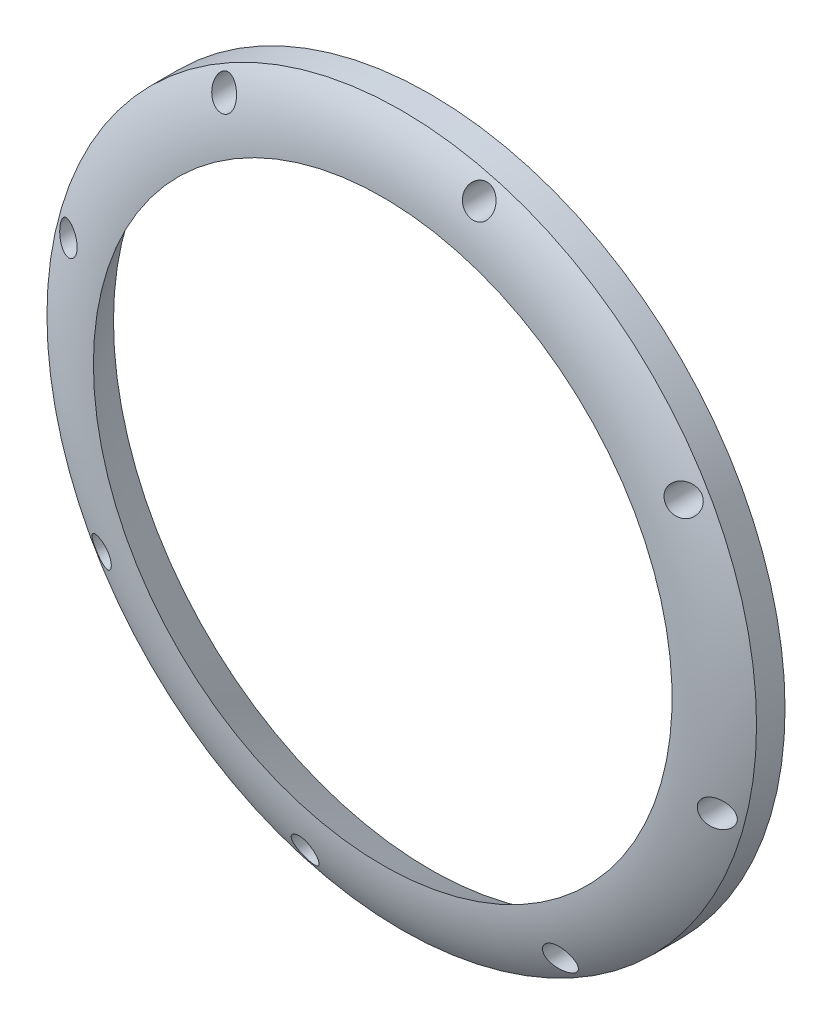
SolidWorks part; units mm, degrees
material "PUR"
ref_plane "Front Plane" through (0, 0, 0) normal (0, 0, 1) x (1, 0, 0)
ref_plane "Top Plane" through (0, 0, 0) normal (0, 1, 0) x (1, 0, 0)
ref_plane "Right Plane" through (0, 0, 0) normal (1, 0, 0) x (0, 0, -1)
sketch "Sketch1" plane through (0, 0, 0) normal (0, 0, 1) x (1, 0, 0)
  circle A0 centre (0, 0) radius 100 construction
  circle A1 centre (0, 0) radius 100
  circle A2 centre (0, 0) radius 112
  arc A3 (111.914, 4.3889) -> (-77.2845, 81.0624) centre (0, 0) ccw construction
sketch "Sketch2" plane through (0, 0, 0) normal (0, 1, 0) x (1, 0, 0)
  line L0 (-112, 0) -> (112, 0) construction
  line L1 (-100, 0) -> (100, 0) construction
  line L2 (-112, 0) -> (112, 0) construction
  line L3 (-100, 0) -> (100, 0) construction
  line L4 (-100, 0) -> (-112, 0)
  line L5 (-100, 0) -> (-91.3397, -15)
  line L6 (0, 0) -> (0, -15) construction
  line L7 (-112, 0) -> (-112, -9)
  line L8 (-91.3397, -15) -> (0, -15) construction
  arc A0 (-91.3397, -15) -> (-112, -9) centre (-91.3397, 23.5705) cw
  point P6 (-112, -5.5901)
  point P8 (0, -16.4787)
  point P11 (-91.2616, -15.1354)
  dimension "D1" = 60
  dimension "D2" = 9
  dimension "D3" = 15
revolve "Revolve1" add sketch "Sketch2" angle 360 about L6
sketch "Sketch3" plane through (0, 0, 0) normal (0, 0, -1) x (-1, 0, 0)
  circle A0 centre (-102.3881, -27.4348) radius 2.65 construction
  circle A1 centre (-102.3881, -27.4348) radius 2.65
extrude "Cut-Extrude1" cut sketch "Sketch3" against normal through all
sketch "Sketch4" plane through (0, 0, 0) normal (0, 0, -1) x (-1, 0, 0)
  circle A0 centre (-102.3881, -27.4348) radius 4.5
  dimension "D1" = 9
extrude "Cut-Extrude2" cut sketch "Sketch4" against normal through all from offset 3 offset against normal yes
pattern_circular "CirPattern1" count 8 over 360 about axis through (0, 0, 0) along (0, 0, -1) of "Cut-Extrude1", "Cut-Extrude2"
